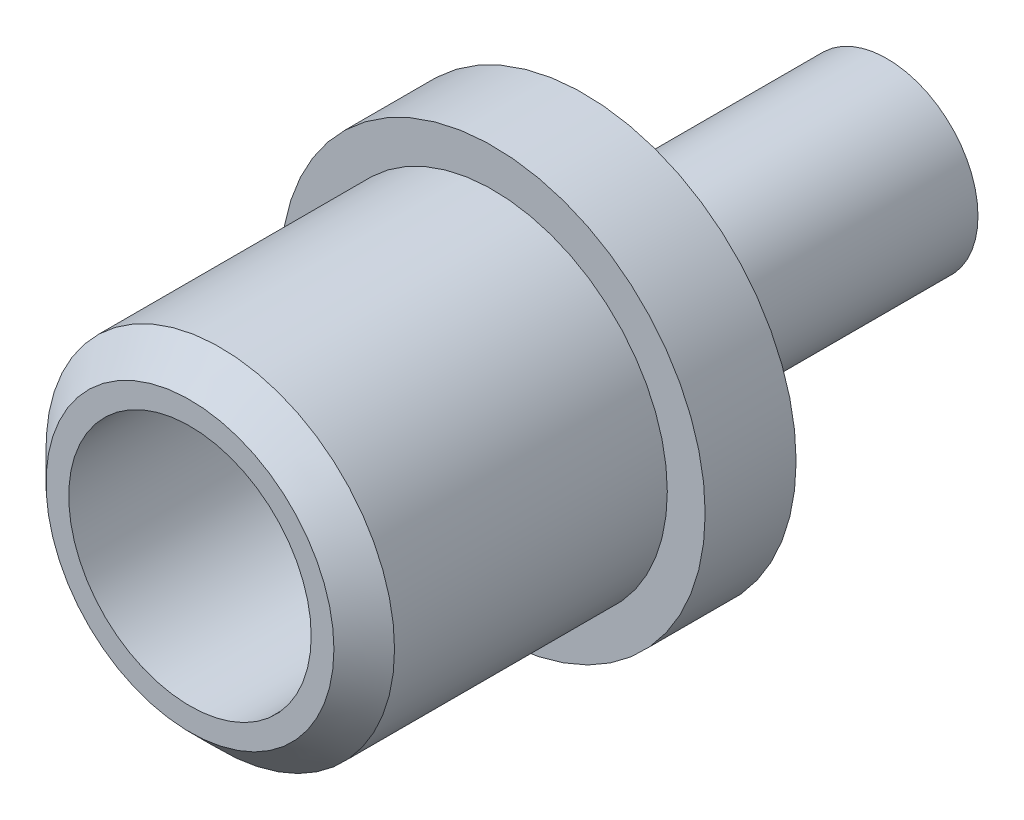
SolidWorks part; units mm, degrees
note: The reader was unsure of these and kept them because the rebuilt part matched: shared geometry of "Sketch1<3>", "Sketch1<4>", "Sketch1<5>".
ref_plane "Front Plane" through (0, 0, 0) normal (0, 0, 1) x (1, 0, 0)
ref_plane "Top Plane" through (0, 0, 0) normal (0, 1, 0) x (1, 0, 0)
ref_plane "Right Plane" through (0, 0, 0) normal (1, 0, 0) x (0, 0, -1)
sketch "Sketch1" plane through (0, 0, 0) normal (0, 0, 1) x (1, 0, 0)
  circle A0 centre (0, 0) radius 3
  circle A1 centre (0, 0) radius 5.75
  circle A3 centre (0, 0) radius 4
  circle A4 centre (0, 0) radius 2
  circle A5 centre (0, 0) radius 7
  dimension "D1" = 6
  dimension "D2" = 8
  dimension "D3" = 11.5
  dimension "D4" = 4
extrude "Boss-Extrude1" add sketch "Sketch1" along normal blind 10 contours A1 A0
extrude "Boss-Extrude2" add sketch "Sketch1<3>" against normal blind 3 contours A1 A0 | A0 A3
sketch "Sketch1<3>" plane through (0, 0, 0) normal (0, 0, 1) x (1, 0, 0) same geometry as "Sketch1"
extrude "Boss-Extrude3" add sketch "Sketch1<4>" against normal blind 13 contours A3 A4
sketch "Sketch1<4>" plane through (0, 0, 0) normal (0, 0, 1) x (1, 0, 0) same geometry as "Sketch1"
extrude "Boss-Extrude4" add sketch "Sketch1<5>" against normal blind 3 contours A5 A1
sketch "Sketch1<5>" plane through (0, 0, 0) normal (0, 0, 1) x (1, 0, 0) same geometry as "Sketch1"
fillet "Fillet1" radius 10 1 edges at (2, 0, 0)
chamfer "Chamfer1" distance 1 angle 45 1 edges at (5.75, 0, 10)
